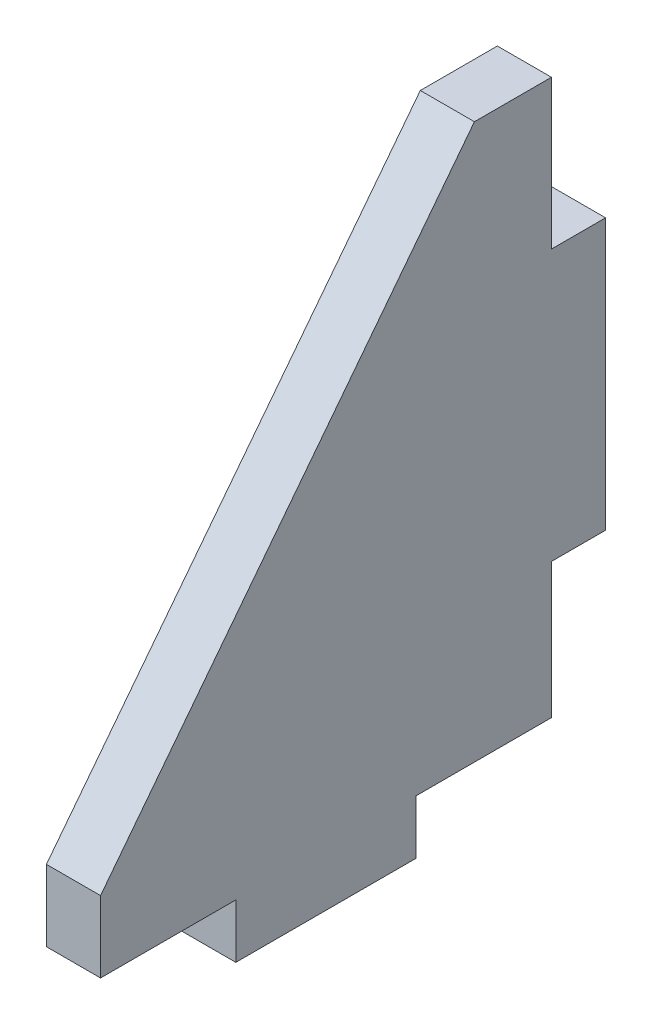
SolidWorks part; units mm, degrees
ref_plane "Front Plane" through (0, 0, 0) normal (0, 0, 1) x (1, 0, 0)
ref_plane "Top Plane" through (0, 0, 0) normal (0, 1, 0) x (1, 0, 0)
ref_plane "Right Plane" through (0, 0, 0) normal (1, 0, 0) x (0, 0, -1)
sketch "Sketch1" plane through (0, 0, 0) normal (0, 0, 1) x (1, 0, 0)
  line L0 (0, -19) -> (6, -19)
  line L1 (0, 27.4983) -> (6, 27.4983)
  line L2 (0, 27.4983) -> (0, -40)
  line L3 (0, -40) -> (6, -40)
  line L4 (6, 27.4983) -> (6, -40)
  line L5 (0, 11) -> (6, 11)
  point P4 (0, 0)
  point P5 (0, 0)
  point P8 (0, 0)
  point P9 (0, 0)
  dimension "D1" = 6
  dimension "D2" = 67.4983
  dimension "D3" = 21
  dimension "D4" = 30
extrude "Boss-Extrude1" add sketch "Sketch1" along normal blind 50 contours L2 L5 L4 L1 | L5 L2 L0 L4 | L4 L0 L2 L3 region at (3, -4, 0) region at (3, -29.5, 0) region at (3, 19.2492, 0)
extrude "Boss-Extrude2" add sketch "Sketch1<3>" against normal blind 6 contours L5 L2 L0 L4 region at (3, -4, 0)
sketch "Sketch1<3>" plane through (0, 0, 0) normal (0, 0, 1) x (1, 0, 0) same geometry as "Sketch1"
sketch "Sketch2" plane through (0, 0, 0) normal (-1, 0, 0) x (0, 0, 1)
  line L0 (0, -34) -> (15, -34)
  line L1 (0, -19) -> (0, -40) construction
  line L2 (15, -34) -> (15, -40)
  line L3 (50, -40) -> (0, -40) construction
  line L4 (15, -40) -> (35, -40)
  line L5 (0, -34) -> (0, -43.1591)
  line L6 (0, -43.1591) -> (50, -43.1591)
  line L7 (25, -40) -> (25, -43.1591) construction
  line L8 (50, -34) -> (50, -43.1591)
  line L9 (50, -34) -> (35, -34)
  line L10 (35, -34) -> (35, -40)
  dimension "D1" = 20
  dimension "D2" = 6
extrude "Cut-Extrude1" cut sketch "Sketch2" against normal blind 6
sketch "Sketch3" plane through (0, 0, 0) normal (-1, 0, 0) x (0, 0, 1)
  line L0 (8.5425, 27.4983) -> (50, -26.0859)
  line L1 (50, 27.4983) -> (0, 27.4983) construction
  line L2 (50, 27.4983) -> (50, -34) construction
  line L3 (50, -26.0859) -> (50, 27.4983)
  line L4 (50, 27.4983) -> (8.5425, 27.4983)
extrude "Cut-Extrude2" cut sketch "Sketch3" against normal blind 6
